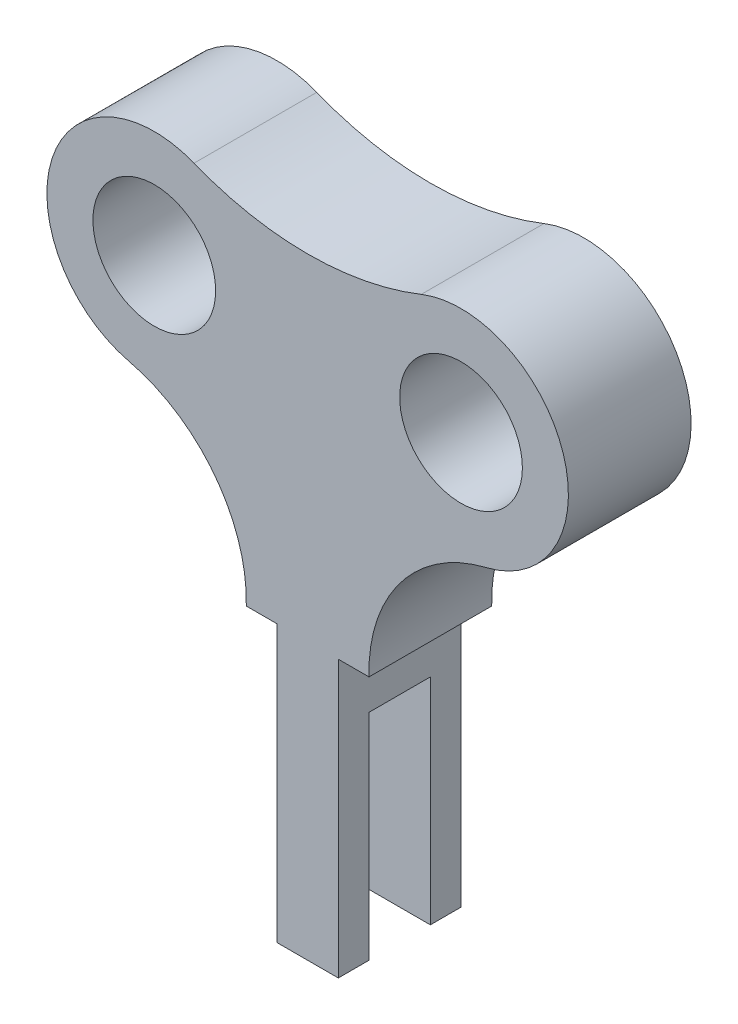
SolidWorks part; units mm, degrees
ref_plane "Front Plane" through (0, 0, 0) normal (0, 0, 1) x (1, 0, 0)
ref_plane "Top Plane" through (0, 0, 0) normal (0, 1, 0) x (1, 0, 0)
ref_plane "Right Plane" through (0, 0, 0) normal (1, 0, 0) x (0, 0, -1)
sketch "Sketch3" plane through (0, 0, 0) normal (0, 0, 1) x (1, 0, 0)
  line L0 (0, 57.753) -> (0, -57.753) construction
  line L1 (5, -50.1008) -> (-5, -50.1008)
  line L2 (-5, -50.1008) -> (-5, -5.1008)
  line L3 (-5, -5.1008) -> (-10, -5.1008)
  line L4 (5, -50.1008) -> (5, -5.1008)
  line L5 (5, -5.1008) -> (10, -5.1008)
  circle A0 centre (-25, 36.8992) radius 10
  circle A1 centre (25, 36.8992) radius 10
  arc A2 (-18.5185, 53.1547) -> (-29.1137, 19.8896) centre (-25, 36.8992) ccw
  arc A3 (29.1137, 19.8896) -> (18.5185, 53.1547) centre (25, 36.8992) ccw
  arc A4 (-18.5185, 53.1547) -> (18.5185, 53.1547) centre (0, 99.5989) ccw
  arc A5 (-29.1137, 19.8896) -> (-10, -5.1008) centre (-34.9905, -4.4099) cw
  arc A6 (29.1137, 19.8896) -> (10, -5.1008) centre (34.9905, -4.4099) ccw
  point P13 (0, 0)
  point P20 (0, -50.1008)
  dimension "D1" = 20
  dimension "D2" = 20
  dimension "D4" = 35
  dimension "D6" = 50
  dimension "D11" = 25
  dimension "D3" = 50
  dimension "D7" = 5
  dimension "D8" = 45
  dimension "D9" = 5
  dimension "D10" = 87
extrude "Boss-Extrude1" add sketch "Sketch3" along normal blind 10 and the other way blind 10
sketch "Sketch6" plane through (0, -50.1008, 0) normal (0, -1, 0) x (1, 0, 0)
  line L0 (5, -10) -> (5, 10) construction
  line L1 (-5, 5) -> (5, 5)
  line L2 (-5, 5) -> (-5, -5)
  line L3 (-5, -5) -> (5, -5)
  line L4 (5, 5) -> (5, -5)
  line L5 (-5, 5) -> (5, -5) construction
  line L6 (-5, -5) -> (5, 5) construction
  point P0 (0, 0)
  dimension "D1" = 10
extrude "Cut-Extrude1" cut sketch "Sketch6" against normal blind 35
